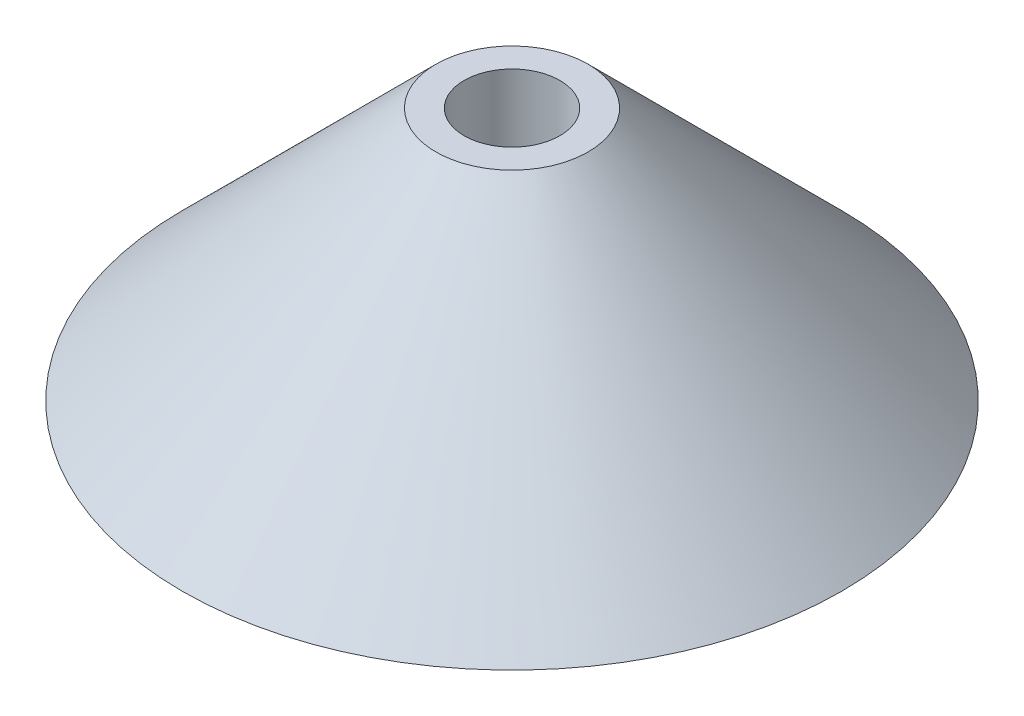
SolidWorks part; units mm, degrees
ref_plane "Ebene vorne" through (0, 0, 0) normal (0, 0, 1) x (1, 0, 0)
ref_plane "Ebene oben" through (0, 0, 0) normal (0, 1, 0) x (1, 0, 0)
ref_plane "Ebene rechts" through (0, 0, 0) normal (1, 0, 0) x (0, 0, -1)
sketch "Sketch1" plane through (0, 0, 0) normal (0, 0, 1) x (1, 0, 0)
  line L0 (0, 11.3265) -> (0, -9.4898) construction
  line L2 (-2.7, 9) -> (-11.7, 0)
  line L3 (-11.7, 0) -> (-1.7, 0)
  line L4 (-2.7, 9) -> (-1.7, 9)
  line L5 (-1.7, 9) -> (-1.7, 0)
  point P5 (-1.431, 0)
  dimension "D1" = 9
  dimension "D2" = 1
  dimension "D3" = 3.4
  dimension "D4" = 10
revolve "Revolve1" add sketch "Sketch1" angle 360 about L0
